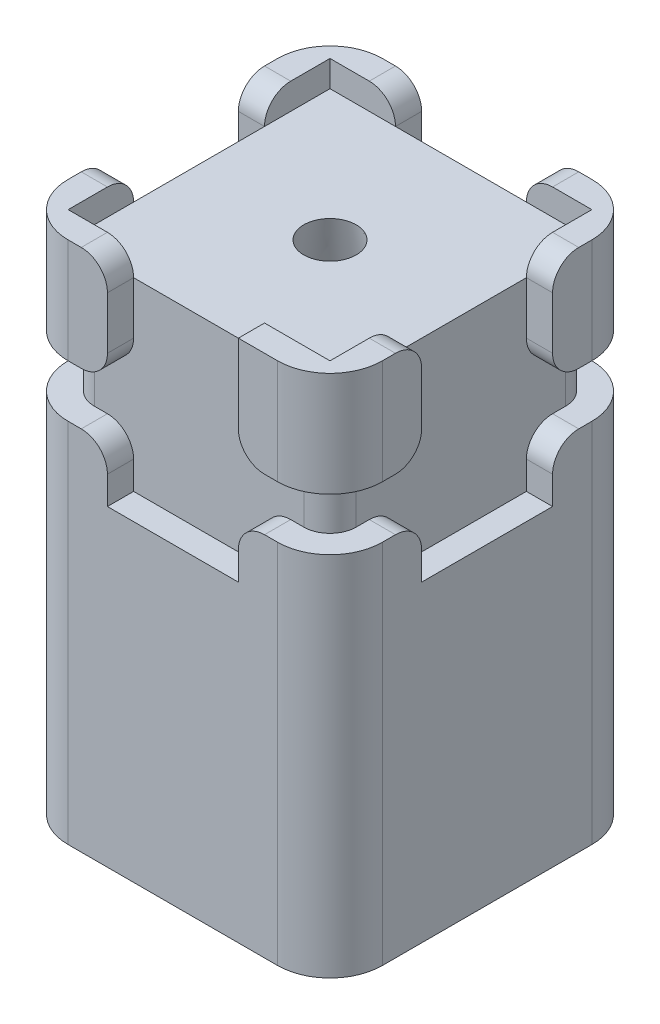
SolidWorks part; units mm, degrees
ref_plane "Front Plane" through (0, 0, 0) normal (0, 0, 1) x (1, 0, 0)
ref_plane "Top Plane" through (0, 0, 0) normal (0, 1, 0) x (1, 0, 0)
ref_plane "Right Plane" through (0, 0, 0) normal (1, 0, 0) x (0, 0, -1)
sketch "Sketch2" plane through (0, 0, 0) normal (0, 1, 0) x (1, 0, 0)
  line L1 (-15, -15) -> (15, -15)
  line L2 (-15, -15) -> (-15, 15)
  line L3 (-15, 15) -> (15, 15)
  line L4 (15, -15) -> (15, 15)
  line L5 (0, 15) -> (0, -15) construction
  line L6 (-15, 0) -> (15, 0) construction
  point P0 (0, 0)
  dimension "D1" = 30
  dimension "D2" = 30
extrude "Boss-Extrude1" add sketch "Sketch2" along normal blind 50
sketch "Sketch3" plane through (0, 50, 0) normal (0, 1, 0) x (1, 0, 0)
  line L1 (-12.5, -12.5) -> (12.5, -12.5)
  line L2 (-12.5, -12.5) -> (-12.5, 12.5)
  line L3 (-12.5, 12.5) -> (12.5, 12.5)
  line L4 (12.5, -12.5) -> (12.5, 12.5)
  line L5 (0, 12.5) -> (0, -12.5) construction
  line L6 (-12.5, 0) -> (12.5, 0) construction
  point P0 (0, 0)
  dimension "D1" = 25
  dimension "D2" = 25
extrude "Cut-Extrude1" cut sketch "Sketch3" against normal blind 2.5
fillet "Fillet1" radius 5 4 edges at (15, 25, 15) (15, 25, -15) (-15, 25, -15) (-15, 25, 15)
sketch "Sketch6" plane through (0, 0, 0) normal (0, -1, 0) x (1, 0, 0)
  circle A0 centre (0, 0) radius 12.5
  dimension "D1" = 25
sketch "Sketch8" plane through (0, 47.5, 0) normal (0, 1, 0) x (1, 0, 0)
  circle A0 centre (0, 0) radius 2.5
  dimension "D1" = 5
loft "Cut-Loft2" cut profiles "Sketch6", "Sketch8" connector at (0, 0, -12.5) connector at (0.7845, 47.5, -2.3737)
sketch "Sketch9" plane through (0, 0, 15) normal (0, 0, 1) x (1, 0, 0)
  line L0 (-10, 50) -> (10, 50) construction
  line L1 (-6.25, 29.8275) -> (6.25, 29.8275)
  line L2 (-6.25, 29.8275) -> (-6.25, 50)
  line L3 (-6.25, 50) -> (6.25, 50)
  line L4 (6.25, 29.8275) -> (6.25, 50)
  line L5 (0, 50) -> (0, 29.8275) construction
  line L6 (-6.25, 39.9138) -> (6.25, 39.9138) construction
  point P0 (0, 39.9138)
  dimension "D1" = 12.5
extrude "Cut-Extrude2" cut sketch "Sketch9" against normal blind 2.5
pattern_circular "CirPattern1" count 4 over 360 about axis through (0, 47.5, 0) along (0, 1, 0) of "Cut-Extrude2", "Cut-Loft2"
ref_plane "Plane1" through (0, 35, 0) normal (0, 1, 0) x (1, 0, 0)
sketch "Sketch10" plane through (0, 35, 0) normal (0, 1, 0) x (1, 0, 0)
  line L2 (5, 6.25) -> (5, 10)
  line L3 (5, 6.25) -> (5, 10)
  line L27 (12.5, -10) -> (12.5, -6.25)
  line L28 (6.25, -12.5) -> (10, -12.5)
  line L29 (-10, -12.5) -> (-6.25, -12.5)
  line L30 (-6.25, -12.5) -> (6.25, -12.5)
  line L31 (-12.5, -6.25) -> (-12.5, -10)
  line L32 (-12.5, 6.25) -> (-12.5, -6.25)
  line L33 (-12.5, 10) -> (-12.5, 6.25)
  line L34 (-6.25, 12.5) -> (-10, 12.5)
  line L35 (10, 12.5) -> (6.25, 12.5)
  line L36 (6.25, 12.5) -> (-6.25, 12.5)
  line L37 (12.5, 6.25) -> (12.5, 10)
  line L38 (12.5, -6.25) -> (12.5, 6.25)
  line L39 (12.5, -10) -> (12.5, -6.25)
  line L40 (6.25, -12.5) -> (10, -12.5)
  line L41 (-10, -12.5) -> (-6.25, -12.5)
  line L42 (-6.25, -12.5) -> (6.25, -12.5)
  line L43 (-12.5, -6.25) -> (-12.5, -10)
  line L44 (-12.5, 6.25) -> (-12.5, -6.25)
  line L45 (-12.5, 10) -> (-12.5, 6.25)
  line L46 (-6.25, 12.5) -> (-10, 12.5)
  line L47 (10, 12.5) -> (6.25, 12.5)
  line L48 (6.25, 12.5) -> (-6.25, 12.5)
  line L49 (12.5, 6.25) -> (12.5, 10)
  line L50 (12.5, -6.25) -> (12.5, 6.25)
  circle A6 centre (0, 0) radius 21.0554
  arc A10 (10, -12.5) -> (12.5, -10) centre (10, -10) ccw
  arc A11 (-12.5, -10) -> (-10, -12.5) centre (-10, -10) ccw
  arc A12 (-10, 12.5) -> (-12.5, 10) centre (-10, 10) ccw
  arc A13 (12.5, 10) -> (10, 12.5) centre (10, 10) ccw
  arc A14 (10, -12.5) -> (12.5, -10) centre (10, -10) ccw
  arc A15 (-12.5, -10) -> (-10, -12.5) centre (-10, -10) ccw
  arc A16 (-10, 12.5) -> (-12.5, 10) centre (-10, 10) ccw
  arc A17 (12.5, 10) -> (10, 12.5) centre (10, 10) ccw
  dimension "D1" = 10
  dimension "D2" = 2.5
extrude "Cut-Extrude4" cut sketch "Sketch10" along normal blind 5 contours A6 A17 L49 L50 L39 A14 L40 L42 L41 A15 L43 L44 L45 A16 L46 L48 L47 region at (-20.4599, 35, 0)
fillet "Fillet2" radius 2.5 23 edges at (-13.75, 35, 6.25) (-13.75, 35, -6.25) (6.25, 35, -13.75) (-6.25, 35, -13.75) (13.75, 35, -6.25) (13.75, 35, 6.25) (6.25, 35, 13.75) (-6.25, 35, 13.75) (-13.75, 40, 6.25) (-13.75, 40, -6.25) (-6.25, 40, -13.75) (6.25, 40, -13.75) (6.25, 40, 13.75) (13.75, 40, 6.25) (13.75, 40, -6.25) (13.75, 50, 6.25) (13.75, 50, -6.25) (6.25, 50, -13.75) (-6.25, 50, -13.75) (-13.75, 50, -6.25) (-13.75, 50, 6.25) (-6.25, 50, 13.75) (-6.25, 40, 13.75)
